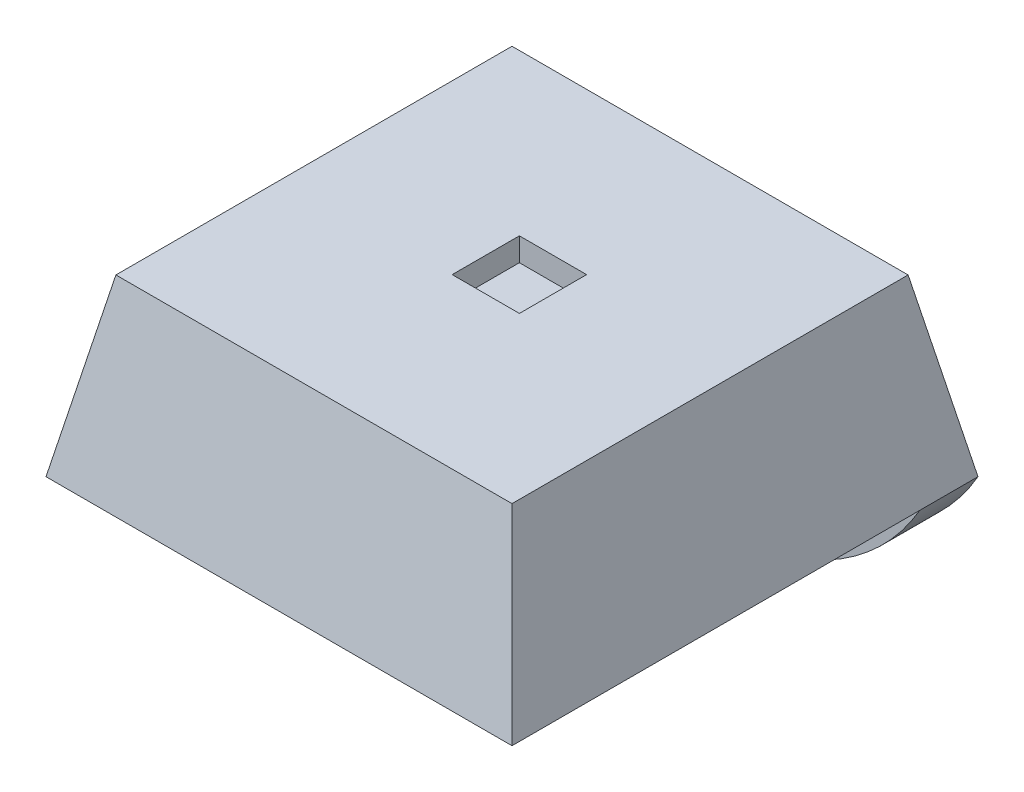
SolidWorks part; units mm, degrees
ref_plane "Front Plane" through (0, 0, 0) normal (0, 0, 1) x (1, 0, 0)
ref_plane "Top Plane" through (0, 0, 0) normal (0, 1, 0) x (1, 0, 0)
ref_plane "Right Plane" through (0, 0, 0) normal (1, 0, 0) x (0, 0, -1)
sketch "Sketch1" plane through (0, 0, 0) normal (0, 1, 0) x (1, 0, 0)
  line L1 (0, 0) -> (8, 0)
  line L2 (0, 0) -> (0, 8)
  line L3 (0, 8) -> (8, 8)
  line L4 (8, 0) -> (8, 8)
  dimension "D1" = 8
  dimension "D2" = 8
extrude "Boss-Extrude1" add sketch "Sketch1" along normal blind 3
sketch "Sketch2" plane through (0, 0, 0) normal (0, 0, 1) x (1, 0, 0)
  line L0 (0, 0) -> (0.6, 3)
  line L1 (0, 3) -> (8, 3) construction
  line L2 (0.6, 3) -> (0, 3)
  line L3 (0, 3) -> (0, 0)
  line L4 (8, 0) -> (7.4, 3)
  line L5 (7.4, 3) -> (8, 3)
  line L6 (8, 3) -> (8, 0)
  dimension "D1" = 0.6
  dimension "D2" = 0.6
extrude "Cut-Extrude1" cut sketch "Sketch2" against normal through all both and the other way through all
sketch "Sketch3" plane through (0, 0, 0) normal (1, 0, 0) x (0, 0, -1)
  line L0 (0, 0) -> (0.6, 3)
  line L1 (8, 3) -> (0, 3) construction
  line L2 (0.6, 3) -> (0, 3)
  line L3 (0, 3) -> (0, 0)
  line L4 (8, 3) -> (7.4, 3)
  line L5 (7.4, 3) -> (8, 0)
  line L6 (8, 3) -> (8, 0)
  dimension "D1" = 0.6
  dimension "D2" = 0.6
extrude "Cut-Extrude2" cut sketch "Sketch3" along normal blind 11
sketch "Sketch4" plane through (0, 0, 0) normal (0, -1, 0) x (1, 0, 0)
  line L0 (8, 0) -> (8, -8) construction
  line L3 (0, 0) -> (8, 0) construction
  circle A0 centre (4, -3.75) radius 1.75
  dimension "D1" = 3.5
  dimension "D2" = 4
  dimension "D3" = 3.75
extrude "Cut-Extrude3" cut sketch "Sketch4" against normal blind 0.4
sketch "Sketch5" plane through (0, 0, 0) normal (0, -1, 0) x (1, 0, 0)
  line L0 (8, 0) -> (8, -8) construction
  line L1 (0, -8) -> (8, -8)
  line L2 (0, -8) -> (0, -7)
  line L3 (0, -7) -> (8, -7)
  line L4 (8, -8) -> (8, -7)
  dimension "D1" = 1
extrude "Boss-Extrude2" add sketch "Sketch5" along normal blind 2
fillet "Fillet1" radius 4 2 edges at (8, -2, -7.5) (0, -2, -7.5)
sketch "Sketch6" plane through (0, 3, 0) normal (0, 1, 0) x (1, 0, 0)
  text T0 "." font "Arial" height 6
extrude "Cut-Extrude4" cut sketch "Sketch6" against normal blind 0.4
